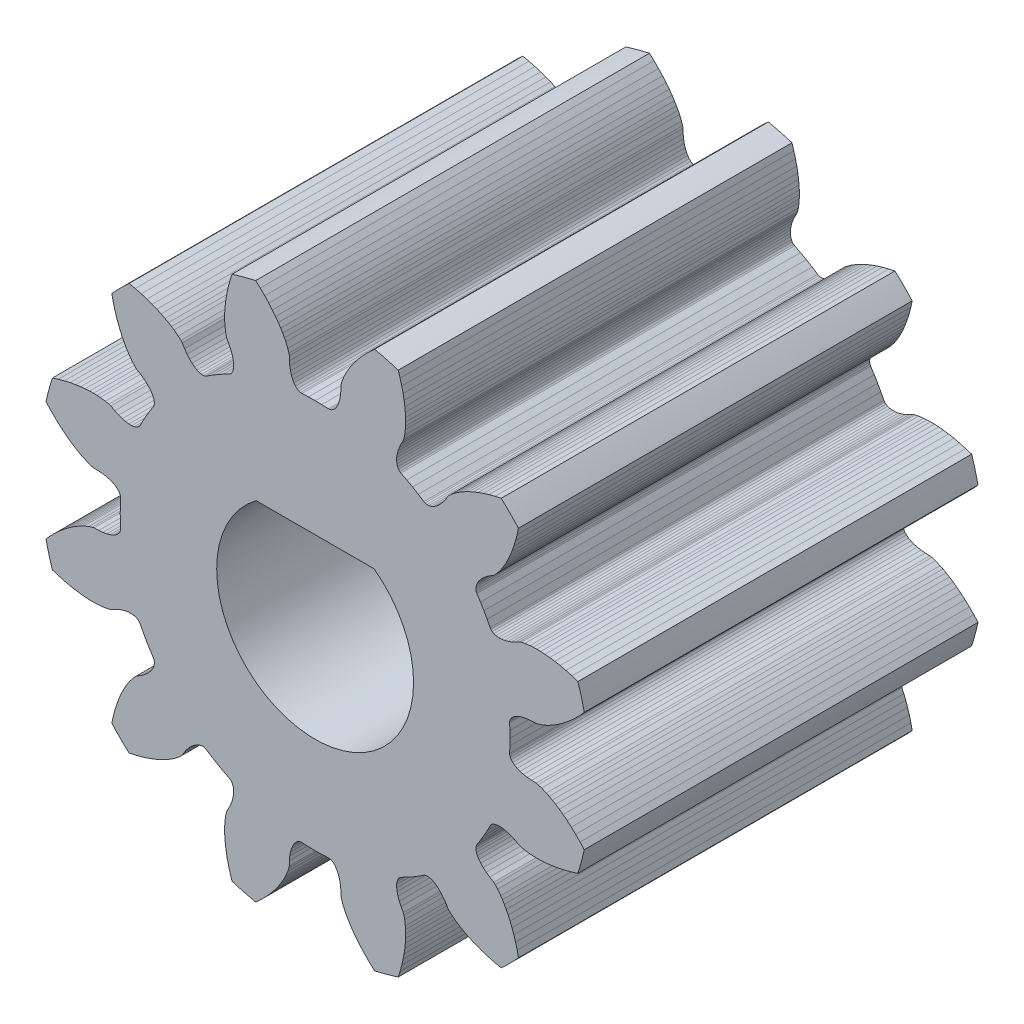
SolidWorks part; units mm, degrees
ref_plane "Front Plane" through (0, 0, 0) normal (0, 0, 1) x (1, 0, 0)
ref_plane "Top Plane" through (0, 0, 0) normal (0, 1, 0) x (1, 0, 0)
ref_plane "Right Plane" through (0, 0, 0) normal (1, 0, 0) x (0, 0, -1)
sketch "Model" plane through (0, 0, 0) normal (0, 0, 1) x (1, 0, 0)
  line L0 (25.8694, -4.5708) -> (25.9098, -4.4161)
  line L1 (25.9098, -4.4161) -> (25.9538, -4.2725)
  line L2 (25.9538, -4.2725) -> (26.0003, -4.1408)
  line L3 (26.0003, -4.1408) -> (26.0488, -4.0198)
  line L4 (26.0488, -4.0198) -> (26.0977, -3.9112)
  line L5 (26.0977, -3.9112) -> (26.1475, -3.8119)
  line L6 (26.1475, -3.8119) -> (26.1956, -3.7252)
  line L7 (26.1956, -3.7252) -> (26.2429, -3.6478)
  line L8 (26.2429, -3.6478) -> (26.2875, -3.5813)
  line L9 (26.2875, -3.5813) -> (26.3671, -3.477)
  line L10 (26.3671, -3.477) -> (26.4285, -3.4089)
  line L11 (26.4285, -3.4089) -> (26.466, -3.3746)
  line L12 (26.466, -3.3746) -> (26.5668, -3.3141)
  line L13 (26.5668, -3.3141) -> (26.6547, -3.2516)
  line L14 (26.6547, -3.2516) -> (26.7296, -3.1879)
  line L15 (26.7296, -3.1879) -> (26.7917, -3.1241)
  line L16 (26.7917, -3.1241) -> (26.841, -3.0611)
  line L17 (26.841, -3.0611) -> (26.8779, -2.9999)
  line L18 (26.8779, -2.9999) -> (26.9025, -2.9414)
  line L19 (26.9025, -2.9414) -> (26.9152, -2.8864)
  line L20 (26.9152, -2.8864) -> (26.9163, -2.836)
  line L21 (26.9163, -2.836) -> (26.9062, -2.7909)
  line L22 (26.9062, -2.7909) -> (26.8916, -2.7611)
  line L23 (26.8916, -2.7611) -> (26.8003, -2.6202)
  line L24 (26.8003, -2.6202) -> (26.7132, -2.475)
  line L25 (26.7132, -2.475) -> (26.631, -2.327)
  line L26 (26.631, -2.327) -> (26.5546, -2.1774)
  line L27 (26.5546, -2.1774) -> (26.5361, -2.1499)
  line L28 (26.5361, -2.1499) -> (26.5021, -2.1186)
  line L29 (26.5021, -2.1186) -> (26.4579, -2.0943)
  line L30 (26.4579, -2.0943) -> (26.404, -2.0778)
  line L31 (26.404, -2.0778) -> (26.341, -2.0699)
  line L32 (26.341, -2.0699) -> (26.2695, -2.0712)
  line L33 (26.2695, -2.0712) -> (26.1903, -2.0825)
  line L34 (26.1903, -2.0825) -> (26.104, -2.1043)
  line L35 (26.104, -2.1043) -> (26.0114, -2.1374)
  line L36 (26.0114, -2.1374) -> (25.9133, -2.1822)
  line L37 (25.9133, -2.1822) -> (25.8106, -2.2393)
  line L38 (25.8106, -2.2393) -> (25.762, -2.2546)
  line L39 (25.762, -2.2546) -> (25.6724, -2.2738)
  line L40 (25.6724, -2.2738) -> (25.5422, -2.2905)
  line L41 (25.5422, -2.2905) -> (25.4624, -2.2959)
  line L42 (25.4624, -2.2959) -> (25.3717, -2.2981)
  line L43 (25.3717, -2.2981) -> (25.2725, -2.2965)
  line L44 (25.2725, -2.2965) -> (25.1616, -2.2899)
  line L45 (25.1616, -2.2899) -> (25.0431, -2.278)
  line L46 (25.0431, -2.278) -> (24.9141, -2.2595)
  line L47 (24.9141, -2.2595) -> (24.7768, -2.2339)
  line L48 (24.7768, -2.2339) -> (24.6305, -2.2002)
  line L49 (24.6305, -2.2002) -> (24.4762, -2.1578)
  line L50 (24.4762, -2.1578) -> (24.3255, -2.1096)
  line L51 (24.1649, -1.5103) -> (24.2713, -1.3932)
  line L52 (24.2713, -1.3932) -> (24.3837, -1.2793)
  line L53 (24.3837, -1.2793) -> (24.4936, -1.177)
  line L54 (24.4936, -1.177) -> (24.5997, -1.0861)
  line L55 (24.5997, -1.0861) -> (24.7022, -1.0056)
  line L56 (24.7022, -1.0056) -> (24.7988, -0.9361)
  line L57 (24.7988, -0.9361) -> (24.8916, -0.875)
  line L58 (24.8916, -0.875) -> (24.9767, -0.8239)
  line L59 (24.9767, -0.8239) -> (25.0563, -0.7805)
  line L60 (25.0563, -0.7805) -> (25.1282, -0.7452)
  line L61 (25.1282, -0.7452) -> (25.2493, -0.6947)
  line L62 (25.2493, -0.6947) -> (25.3365, -0.6665)
  line L63 (25.3365, -0.6665) -> (25.3862, -0.6555)
  line L64 (25.3862, -0.6555) -> (25.5037, -0.6535)
  line L65 (25.5037, -0.6535) -> (25.611, -0.6433)
  line L66 (25.611, -0.6433) -> (25.7078, -0.6256)
  line L67 (25.7078, -0.6256) -> (25.7934, -0.6014)
  line L68 (25.7934, -0.6014) -> (25.8677, -0.5716)
  line L69 (25.8677, -0.5716) -> (25.9302, -0.537)
  line L70 (25.9302, -0.537) -> (25.9808, -0.4986)
  line L71 (25.9808, -0.4986) -> (26.0192, -0.4573)
  line L72 (26.0192, -0.4573) -> (26.0454, -0.4142)
  line L73 (26.0454, -0.4142) -> (26.0592, -0.3701)
  line L74 (26.0592, -0.3701) -> (26.0614, -0.337)
  line L75 (26.0614, -0.337) -> (26.0529, -0.1693)
  line L76 (26.0529, -0.1693) -> (26.05, 0)
  line L77 (26.05, 0) -> (26.0529, 0.1693)
  line L78 (26.0529, 0.1693) -> (26.0614, 0.337)
  line L79 (26.0614, 0.337) -> (26.0592, 0.3701)
  line L80 (26.0592, 0.3701) -> (26.0454, 0.4142)
  line L81 (26.0454, 0.4142) -> (26.0192, 0.4573)
  line L82 (26.0192, 0.4573) -> (25.9808, 0.4986)
  line L83 (25.9808, 0.4986) -> (25.9302, 0.537)
  line L84 (25.9302, 0.537) -> (25.8677, 0.5716)
  line L85 (25.8677, 0.5716) -> (25.7934, 0.6014)
  line L86 (25.7934, 0.6014) -> (25.7078, 0.6256)
  line L87 (25.7078, 0.6256) -> (25.611, 0.6433)
  line L88 (25.611, 0.6433) -> (25.5037, 0.6535)
  line L89 (25.5037, 0.6535) -> (25.3862, 0.6555)
  line L90 (25.3862, 0.6555) -> (25.3365, 0.6665)
  line L91 (25.3365, 0.6665) -> (25.2493, 0.6947)
  line L92 (25.2493, 0.6947) -> (25.1282, 0.7452)
  line L93 (25.1282, 0.7452) -> (25.0563, 0.7805)
  line L94 (25.0563, 0.7805) -> (24.9767, 0.8239)
  line L95 (24.9767, 0.8239) -> (24.8916, 0.875)
  line L96 (24.8916, 0.875) -> (24.7988, 0.9361)
  line L97 (24.7988, 0.9361) -> (24.7022, 1.0056)
  line L98 (24.7022, 1.0056) -> (24.5997, 1.0861)
  line L99 (24.5997, 1.0861) -> (24.4936, 1.177)
  line L100 (24.4936, 1.177) -> (24.3837, 1.2793)
  line L101 (24.3837, 1.2793) -> (24.2713, 1.3932)
  line L102 (24.2713, 1.3932) -> (24.1649, 1.5103)
  line L103 (24.3255, 2.1096) -> (24.4762, 2.1578)
  line L104 (24.4762, 2.1578) -> (24.6305, 2.2002)
  line L105 (24.6305, 2.2002) -> (24.7768, 2.2339)
  line L106 (24.7768, 2.2339) -> (24.9141, 2.2595)
  line L107 (24.9141, 2.2595) -> (25.0431, 2.278)
  line L108 (25.0431, 2.278) -> (25.1616, 2.2899)
  line L109 (25.1616, 2.2899) -> (25.2725, 2.2965)
  line L110 (25.2725, 2.2965) -> (25.3717, 2.2981)
  line L111 (25.3717, 2.2981) -> (25.4624, 2.2959)
  line L112 (25.4624, 2.2959) -> (25.5422, 2.2905)
  line L113 (25.5422, 2.2905) -> (25.6724, 2.2738)
  line L114 (25.6724, 2.2738) -> (25.762, 2.2546)
  line L115 (25.762, 2.2546) -> (25.8106, 2.2393)
  line L116 (25.8106, 2.2393) -> (25.9133, 2.1822)
  line L117 (25.9133, 2.1822) -> (26.0114, 2.1374)
  line L118 (26.0114, 2.1374) -> (26.104, 2.1043)
  line L119 (26.104, 2.1043) -> (26.1903, 2.0825)
  line L120 (26.1903, 2.0825) -> (26.2695, 2.0712)
  line L121 (26.2695, 2.0712) -> (26.341, 2.0699)
  line L122 (26.341, 2.0699) -> (26.404, 2.0778)
  line L123 (26.404, 2.0778) -> (26.4579, 2.0943)
  line L124 (26.4579, 2.0943) -> (26.5021, 2.1186)
  line L125 (26.5021, 2.1186) -> (26.5361, 2.1499)
  line L126 (26.5361, 2.1499) -> (26.5546, 2.1774)
  line L127 (26.5546, 2.1774) -> (26.631, 2.327)
  line L128 (26.631, 2.327) -> (26.7132, 2.475)
  line L129 (26.7132, 2.475) -> (26.8003, 2.6202)
  line L130 (26.8003, 2.6202) -> (26.8916, 2.7611)
  line L131 (26.8916, 2.7611) -> (26.9062, 2.7909)
  line L132 (26.9062, 2.7909) -> (26.9163, 2.836)
  line L133 (26.9163, 2.836) -> (26.9152, 2.8864)
  line L134 (26.9152, 2.8864) -> (26.9025, 2.9414)
  line L135 (26.9025, 2.9414) -> (26.8779, 2.9999)
  line L136 (26.8779, 2.9999) -> (26.841, 3.0611)
  line L137 (26.841, 3.0611) -> (26.7917, 3.1241)
  line L138 (26.7917, 3.1241) -> (26.7296, 3.1879)
  line L139 (26.7296, 3.1879) -> (26.6547, 3.2516)
  line L140 (26.6547, 3.2516) -> (26.5668, 3.3141)
  line L141 (26.5668, 3.3141) -> (26.466, 3.3746)
  line L142 (26.466, 3.3746) -> (26.4285, 3.4089)
  line L143 (26.4285, 3.4089) -> (26.3671, 3.477)
  line L144 (26.3671, 3.477) -> (26.2875, 3.5813)
  line L145 (26.2875, 3.5813) -> (26.2429, 3.6478)
  line L146 (26.2429, 3.6478) -> (26.1956, 3.7252)
  line L147 (26.1956, 3.7252) -> (26.1475, 3.8119)
  line L148 (26.1475, 3.8119) -> (26.0977, 3.9112)
  line L149 (26.0977, 3.9112) -> (26.0488, 4.0198)
  line L150 (26.0488, 4.0198) -> (26.0003, 4.1408)
  line L151 (26.0003, 4.1408) -> (25.9538, 4.2725)
  line L152 (25.9538, 4.2725) -> (25.9098, 4.4161)
  line L153 (25.9098, 4.4161) -> (25.8694, 4.5708)
  line L154 (25.8694, 4.5708) -> (25.8358, 4.7255)
  line L155 (26.2745, 5.1642) -> (26.4292, 5.1306)
  line L156 (26.4292, 5.1306) -> (26.5839, 5.0902)
  line L157 (26.5839, 5.0902) -> (26.7275, 5.0462)
  line L158 (26.7275, 5.0462) -> (26.8592, 4.9997)
  line L159 (26.8592, 4.9997) -> (26.9802, 4.9512)
  line L160 (26.9802, 4.9512) -> (27.0888, 4.9023)
  line L161 (27.0888, 4.9023) -> (27.1881, 4.8525)
  line L162 (27.1881, 4.8525) -> (27.2748, 4.8044)
  line L163 (27.2748, 4.8044) -> (27.3522, 4.7571)
  line L164 (27.3522, 4.7571) -> (27.4187, 4.7125)
  line L165 (27.4187, 4.7125) -> (27.523, 4.6329)
  line L166 (27.523, 4.6329) -> (27.5911, 4.5715)
  line L167 (27.5911, 4.5715) -> (27.6254, 4.534)
  line L168 (27.6254, 4.534) -> (27.6859, 4.4332)
  line L169 (27.6859, 4.4332) -> (27.7484, 4.3453)
  line L170 (27.7484, 4.3453) -> (27.8121, 4.2704)
  line L171 (27.8121, 4.2704) -> (27.8759, 4.2083)
  line L172 (27.8759, 4.2083) -> (27.9389, 4.159)
  line L173 (27.9389, 4.159) -> (28.0001, 4.1221)
  line L174 (28.0001, 4.1221) -> (28.0586, 4.0975)
  line L175 (28.0586, 4.0975) -> (28.1136, 4.0848)
  line L176 (28.1136, 4.0848) -> (28.164, 4.0837)
  line L177 (28.164, 4.0837) -> (28.2091, 4.0938)
  line L178 (28.2091, 4.0938) -> (28.2389, 4.1084)
  line L179 (28.2389, 4.1084) -> (28.3798, 4.1997)
  line L180 (28.3798, 4.1997) -> (28.525, 4.2868)
  line L181 (28.525, 4.2868) -> (28.673, 4.369)
  line L182 (28.673, 4.369) -> (28.8226, 4.4454)
  line L183 (28.8226, 4.4454) -> (28.8501, 4.4639)
  line L184 (28.8501, 4.4639) -> (28.8814, 4.4979)
  line L185 (28.8814, 4.4979) -> (28.9057, 4.5421)
  line L186 (28.9057, 4.5421) -> (28.9222, 4.596)
  line L187 (28.9222, 4.596) -> (28.9301, 4.659)
  line L188 (28.9301, 4.659) -> (28.9288, 4.7305)
  line L189 (28.9288, 4.7305) -> (28.9175, 4.8097)
  line L190 (28.9175, 4.8097) -> (28.8957, 4.896)
  line L191 (28.8957, 4.896) -> (28.8626, 4.9886)
  line L192 (28.8626, 4.9886) -> (28.8178, 5.0867)
  line L193 (28.8178, 5.0867) -> (28.7607, 5.1894)
  line L194 (28.7607, 5.1894) -> (28.7454, 5.238)
  line L195 (28.7454, 5.238) -> (28.7262, 5.3276)
  line L196 (28.7262, 5.3276) -> (28.7095, 5.4578)
  line L197 (28.7095, 5.4578) -> (28.7041, 5.5376)
  line L198 (28.7041, 5.5376) -> (28.7019, 5.6283)
  line L199 (28.7019, 5.6283) -> (28.7035, 5.7275)
  line L200 (28.7035, 5.7275) -> (28.7101, 5.8384)
  line L201 (28.7101, 5.8384) -> (28.722, 5.9569)
  line L202 (28.722, 5.9569) -> (28.7405, 6.0859)
  line L203 (28.7405, 6.0859) -> (28.7661, 6.2232)
  line L204 (28.7661, 6.2232) -> (28.7998, 6.3695)
  line L205 (28.7998, 6.3695) -> (28.8422, 6.5238)
  line L206 (28.8422, 6.5238) -> (28.8904, 6.6745)
  line L207 (29.4897, 6.8351) -> (29.6069, 6.7287)
  line L208 (29.6069, 6.7287) -> (29.7207, 6.6163)
  line L209 (29.7207, 6.6163) -> (29.823, 6.5064)
  line L210 (29.823, 6.5064) -> (29.9139, 6.4003)
  line L211 (29.9139, 6.4003) -> (29.9944, 6.2978)
  line L212 (29.9944, 6.2978) -> (30.0639, 6.2012)
  line L213 (30.0639, 6.2012) -> (30.125, 6.1084)
  line L214 (30.125, 6.1084) -> (30.1761, 6.0233)
  line L215 (30.1761, 6.0233) -> (30.2195, 5.9436)
  line L216 (30.2195, 5.9436) -> (30.2548, 5.8718)
  line L217 (30.2548, 5.8718) -> (30.3053, 5.7507)
  line L218 (30.3053, 5.7507) -> (30.3335, 5.6635)
  line L219 (30.3335, 5.6635) -> (30.3445, 5.6138)
  line L220 (30.3445, 5.6138) -> (30.3465, 5.4963)
  line L221 (30.3465, 5.4963) -> (30.3567, 5.389)
  line L222 (30.3567, 5.389) -> (30.3744, 5.2923)
  line L223 (30.3744, 5.2923) -> (30.3986, 5.2066)
  line L224 (30.3986, 5.2066) -> (30.4285, 5.1323)
  line L225 (30.4285, 5.1323) -> (30.463, 5.0698)
  line L226 (30.463, 5.0698) -> (30.5014, 5.0192)
  line L227 (30.5014, 5.0192) -> (30.5427, 4.9808)
  line L228 (30.5427, 4.9808) -> (30.5858, 4.9546)
  line L229 (30.5858, 4.9546) -> (30.6299, 4.9408)
  line L230 (30.6299, 4.9408) -> (30.663, 4.9386)
  line L231 (30.663, 4.9386) -> (30.8307, 4.9471)
  line L232 (30.8307, 4.9471) -> (31, 4.95)
  line L233 (31, 4.95) -> (31.1693, 4.9471)
  line L234 (31.1693, 4.9471) -> (31.337, 4.9386)
  line L235 (31.337, 4.9386) -> (31.3701, 4.9408)
  line L236 (31.3701, 4.9408) -> (31.4142, 4.9546)
  line L237 (31.4142, 4.9546) -> (31.4573, 4.9808)
  line L238 (31.4573, 4.9808) -> (31.4986, 5.0192)
  line L239 (31.4986, 5.0192) -> (31.537, 5.0698)
  line L240 (31.537, 5.0698) -> (31.5715, 5.1323)
  line L241 (31.5715, 5.1323) -> (31.6014, 5.2066)
  line L242 (31.6014, 5.2066) -> (31.6256, 5.2923)
  line L243 (31.6256, 5.2923) -> (31.6433, 5.389)
  line L244 (31.6433, 5.389) -> (31.6535, 5.4963)
  line L245 (31.6535, 5.4963) -> (31.6555, 5.6138)
  line L246 (31.6555, 5.6138) -> (31.6665, 5.6635)
  line L247 (31.6665, 5.6635) -> (31.6947, 5.7507)
  line L248 (31.6947, 5.7507) -> (31.7452, 5.8718)
  line L249 (31.7452, 5.8718) -> (31.7805, 5.9436)
  line L250 (31.7805, 5.9436) -> (31.8239, 6.0233)
  line L251 (31.8239, 6.0233) -> (31.875, 6.1084)
  line L252 (31.875, 6.1084) -> (31.9361, 6.2012)
  line L253 (31.9361, 6.2012) -> (32.0056, 6.2978)
  line L254 (32.0056, 6.2978) -> (32.0862, 6.4003)
  line L255 (32.0862, 6.4003) -> (32.177, 6.5064)
  line L256 (32.177, 6.5064) -> (32.2793, 6.6163)
  line L257 (32.2793, 6.6163) -> (32.3932, 6.7287)
  line L258 (32.3932, 6.7287) -> (32.5103, 6.8351)
  line L259 (33.1096, 6.6745) -> (33.1578, 6.5238)
  line L260 (33.1578, 6.5238) -> (33.2002, 6.3695)
  line L261 (33.2002, 6.3695) -> (33.2339, 6.2232)
  line L262 (33.2339, 6.2232) -> (33.2595, 6.0859)
  line L263 (33.2595, 6.0859) -> (33.278, 5.9569)
  line L264 (33.278, 5.9569) -> (33.2899, 5.8384)
  line L265 (33.2899, 5.8384) -> (33.2965, 5.7275)
  line L266 (33.2965, 5.7275) -> (33.2981, 5.6283)
  line L267 (33.2981, 5.6283) -> (33.2959, 5.5376)
  line L268 (33.2959, 5.5376) -> (33.2905, 5.4578)
  line L269 (33.2905, 5.4578) -> (33.2738, 5.3276)
  line L270 (33.2738, 5.3276) -> (33.2546, 5.238)
  line L271 (33.2546, 5.238) -> (33.2393, 5.1894)
  line L272 (33.2393, 5.1894) -> (33.1822, 5.0867)
  line L273 (33.1822, 5.0867) -> (33.1374, 4.9886)
  line L274 (33.1374, 4.9886) -> (33.1043, 4.896)
  line L275 (33.1043, 4.896) -> (33.0825, 4.8097)
  line L276 (33.0825, 4.8097) -> (33.0712, 4.7305)
  line L277 (33.0712, 4.7305) -> (33.0699, 4.659)
  line L278 (33.0699, 4.659) -> (33.0778, 4.596)
  line L279 (33.0778, 4.596) -> (33.0943, 4.5421)
  line L280 (33.0943, 4.5421) -> (33.1186, 4.4979)
  line L281 (33.1186, 4.4979) -> (33.1499, 4.4639)
  line L282 (33.1499, 4.4639) -> (33.1774, 4.4454)
  line L283 (33.1774, 4.4454) -> (33.327, 4.369)
  line L284 (33.327, 4.369) -> (33.475, 4.2868)
  line L285 (33.475, 4.2868) -> (33.6202, 4.1997)
  line L286 (33.6202, 4.1997) -> (33.7611, 4.1084)
  line L287 (33.7611, 4.1084) -> (33.7909, 4.0938)
  line L288 (33.7909, 4.0938) -> (33.836, 4.0837)
  line L289 (33.836, 4.0837) -> (33.8864, 4.0848)
  line L290 (33.8864, 4.0848) -> (33.9414, 4.0975)
  line L291 (33.9414, 4.0975) -> (33.9999, 4.1221)
  line L292 (33.9999, 4.1221) -> (34.0611, 4.159)
  line L293 (34.0611, 4.159) -> (34.1241, 4.2083)
  line L294 (34.1241, 4.2083) -> (34.1879, 4.2704)
  line L295 (34.1879, 4.2704) -> (34.2516, 4.3453)
  line L296 (34.2516, 4.3453) -> (34.3141, 4.4332)
  line L297 (34.3141, 4.4332) -> (34.3746, 4.534)
  line L298 (34.3746, 4.534) -> (34.4089, 4.5715)
  line L299 (34.4089, 4.5715) -> (34.477, 4.6329)
  line L300 (34.477, 4.6329) -> (34.5813, 4.7125)
  line L301 (34.5813, 4.7125) -> (34.6478, 4.7571)
  line L302 (34.6478, 4.7571) -> (34.7252, 4.8044)
  line L303 (34.7252, 4.8044) -> (34.8119, 4.8525)
  line L304 (34.8119, 4.8525) -> (34.9112, 4.9023)
  line L305 (34.9112, 4.9023) -> (35.0198, 4.9512)
  line L306 (35.0198, 4.9512) -> (35.1408, 4.9997)
  line L307 (35.1408, 4.9997) -> (35.2725, 5.0462)
  line L308 (35.2725, 5.0462) -> (35.4161, 5.0902)
  line L309 (35.4161, 5.0902) -> (35.5708, 5.1306)
  line L310 (35.5708, 5.1306) -> (35.7255, 5.1642)
  line L311 (36.1642, 4.7255) -> (36.1306, 4.5708)
  line L312 (36.1306, 4.5708) -> (36.0902, 4.4161)
  line L313 (36.0902, 4.4161) -> (36.0462, 4.2725)
  line L314 (36.0462, 4.2725) -> (35.9997, 4.1408)
  line L315 (35.9997, 4.1408) -> (35.9512, 4.0198)
  line L316 (35.9512, 4.0198) -> (35.9023, 3.9112)
  line L317 (35.9023, 3.9112) -> (35.8525, 3.8119)
  line L318 (35.8525, 3.8119) -> (35.8044, 3.7252)
  line L319 (35.8044, 3.7252) -> (35.7571, 3.6478)
  line L320 (35.7571, 3.6478) -> (35.7125, 3.5813)
  line L321 (35.7125, 3.5813) -> (35.6329, 3.477)
  line L322 (35.6329, 3.477) -> (35.5715, 3.4089)
  line L323 (35.5715, 3.4089) -> (35.534, 3.3746)
  line L324 (35.534, 3.3746) -> (35.4332, 3.3141)
  line L325 (35.4332, 3.3141) -> (35.3453, 3.2516)
  line L326 (35.3453, 3.2516) -> (35.2704, 3.1879)
  line L327 (35.2704, 3.1879) -> (35.2083, 3.1241)
  line L328 (35.2083, 3.1241) -> (35.159, 3.0611)
  line L329 (35.159, 3.0611) -> (35.1221, 2.9999)
  line L330 (35.1221, 2.9999) -> (35.0975, 2.9414)
  line L331 (35.0975, 2.9414) -> (35.0848, 2.8864)
  line L332 (35.0848, 2.8864) -> (35.0837, 2.836)
  line L333 (35.0837, 2.836) -> (35.0938, 2.7909)
  line L334 (35.0938, 2.7909) -> (35.1084, 2.7611)
  line L335 (35.1084, 2.7611) -> (35.1997, 2.6202)
  line L336 (35.1997, 2.6202) -> (35.2868, 2.475)
  line L337 (35.2868, 2.475) -> (35.369, 2.327)
  line L338 (35.369, 2.327) -> (35.4454, 2.1774)
  line L339 (35.4454, 2.1774) -> (35.4639, 2.1499)
  line L340 (35.4639, 2.1499) -> (35.4979, 2.1186)
  line L341 (35.4979, 2.1186) -> (35.5421, 2.0943)
  line L342 (35.5421, 2.0943) -> (35.596, 2.0778)
  line L343 (35.596, 2.0778) -> (35.659, 2.0699)
  line L344 (35.659, 2.0699) -> (35.7305, 2.0712)
  line L345 (35.7305, 2.0712) -> (35.8097, 2.0825)
  line L346 (35.8097, 2.0825) -> (35.896, 2.1043)
  line L347 (35.896, 2.1043) -> (35.9886, 2.1374)
  line L348 (35.9886, 2.1374) -> (36.0867, 2.1822)
  line L349 (36.0867, 2.1822) -> (36.1894, 2.2393)
  line L350 (36.1894, 2.2393) -> (36.238, 2.2546)
  line L351 (36.238, 2.2546) -> (36.3276, 2.2738)
  line L352 (36.3276, 2.2738) -> (36.4578, 2.2905)
  line L353 (36.4578, 2.2905) -> (36.5376, 2.2959)
  line L354 (36.5376, 2.2959) -> (36.6283, 2.2981)
  line L355 (36.6283, 2.2981) -> (36.7275, 2.2965)
  line L356 (36.7275, 2.2965) -> (36.8384, 2.2899)
  line L357 (36.8384, 2.2899) -> (36.9569, 2.278)
  line L358 (36.9569, 2.278) -> (37.0859, 2.2595)
  line L359 (37.0859, 2.2595) -> (37.2232, 2.2339)
  line L360 (37.2232, 2.2339) -> (37.3695, 2.2002)
  line L361 (37.3695, 2.2002) -> (37.5238, 2.1578)
  line L362 (37.5238, 2.1578) -> (37.6745, 2.1096)
  line L363 (37.8351, 1.5103) -> (37.7287, 1.3932)
  line L364 (37.7287, 1.3932) -> (37.6163, 1.2793)
  line L365 (37.6163, 1.2793) -> (37.5064, 1.177)
  line L366 (37.5064, 1.177) -> (37.4003, 1.0861)
  line L367 (37.4003, 1.0861) -> (37.2978, 1.0056)
  line L368 (37.2978, 1.0056) -> (37.2012, 0.9361)
  line L369 (37.2012, 0.9361) -> (37.1084, 0.875)
  line L370 (37.1084, 0.875) -> (37.0233, 0.8239)
  line L371 (37.0233, 0.8239) -> (36.9436, 0.7805)
  line L372 (36.9436, 0.7805) -> (36.8718, 0.7452)
  line L373 (36.8718, 0.7452) -> (36.7507, 0.6947)
  line L374 (36.7507, 0.6947) -> (36.6635, 0.6665)
  line L375 (36.6635, 0.6665) -> (36.6138, 0.6555)
  line L376 (36.6138, 0.6555) -> (36.4963, 0.6535)
  line L377 (36.4963, 0.6535) -> (36.389, 0.6433)
  line L378 (36.389, 0.6433) -> (36.2923, 0.6256)
  line L379 (36.2923, 0.6256) -> (36.2066, 0.6014)
  line L380 (36.2066, 0.6014) -> (36.1323, 0.5716)
  line L381 (36.1323, 0.5716) -> (36.0698, 0.537)
  line L382 (36.0698, 0.537) -> (36.0192, 0.4986)
  line L383 (36.0192, 0.4986) -> (35.9808, 0.4573)
  line L384 (35.9808, 0.4573) -> (35.9546, 0.4142)
  line L385 (35.9546, 0.4142) -> (35.9408, 0.3701)
  line L386 (35.9408, 0.3701) -> (35.9386, 0.337)
  line L387 (35.9386, 0.337) -> (35.9471, 0.1693)
  line L388 (35.9471, 0.1693) -> (35.95, 0)
  line L389 (35.95, 0) -> (35.9471, -0.1693)
  line L390 (35.9471, -0.1693) -> (35.9386, -0.337)
  line L391 (35.9386, -0.337) -> (35.9408, -0.3701)
  line L392 (35.9408, -0.3701) -> (35.9546, -0.4142)
  line L393 (35.9546, -0.4142) -> (35.9808, -0.4573)
  line L394 (35.9808, -0.4573) -> (36.0192, -0.4986)
  line L395 (36.0192, -0.4986) -> (36.0698, -0.537)
  line L396 (36.0698, -0.537) -> (36.1323, -0.5716)
  line L397 (36.1323, -0.5716) -> (36.2066, -0.6014)
  line L398 (36.2066, -0.6014) -> (36.2923, -0.6256)
  line L399 (36.2923, -0.6256) -> (36.389, -0.6433)
  line L400 (36.389, -0.6433) -> (36.4963, -0.6535)
  line L401 (36.4963, -0.6535) -> (36.6138, -0.6555)
  line L402 (36.6138, -0.6555) -> (36.6635, -0.6665)
  line L403 (36.6635, -0.6665) -> (36.7507, -0.6947)
  line L404 (36.7507, -0.6947) -> (36.8718, -0.7452)
  line L405 (36.8718, -0.7452) -> (36.9436, -0.7805)
  line L406 (36.9436, -0.7805) -> (37.0233, -0.8239)
  line L407 (37.0233, -0.8239) -> (37.1084, -0.875)
  line L408 (37.1084, -0.875) -> (37.2012, -0.9361)
  line L409 (37.2012, -0.9361) -> (37.2978, -1.0056)
  line L410 (37.2978, -1.0056) -> (37.4003, -1.0861)
  line L411 (37.4003, -1.0861) -> (37.5064, -1.177)
  line L412 (37.5064, -1.177) -> (37.6163, -1.2793)
  line L413 (37.6163, -1.2793) -> (37.7287, -1.3932)
  line L414 (37.7287, -1.3932) -> (37.8351, -1.5103)
  line L415 (37.6745, -2.1096) -> (37.5238, -2.1578)
  line L416 (37.5238, -2.1578) -> (37.3695, -2.2002)
  line L417 (37.3695, -2.2002) -> (37.2232, -2.2339)
  line L418 (37.2232, -2.2339) -> (37.0859, -2.2595)
  line L419 (37.0859, -2.2595) -> (36.9569, -2.278)
  line L420 (36.9569, -2.278) -> (36.8384, -2.2899)
  line L421 (36.8384, -2.2899) -> (36.7275, -2.2965)
  line L422 (36.7275, -2.2965) -> (36.6283, -2.2981)
  line L423 (36.6283, -2.2981) -> (36.5376, -2.2959)
  line L424 (36.5376, -2.2959) -> (36.4578, -2.2905)
  line L425 (36.4578, -2.2905) -> (36.3276, -2.2738)
  line L426 (36.3276, -2.2738) -> (36.238, -2.2546)
  line L427 (36.238, -2.2546) -> (36.1894, -2.2393)
  line L428 (36.1894, -2.2393) -> (36.0867, -2.1822)
  line L429 (36.0867, -2.1822) -> (35.9886, -2.1374)
  line L430 (35.9886, -2.1374) -> (35.896, -2.1043)
  line L431 (35.896, -2.1043) -> (35.8097, -2.0825)
  line L432 (35.8097, -2.0825) -> (35.7305, -2.0712)
  line L433 (35.7305, -2.0712) -> (35.659, -2.0699)
  line L434 (35.659, -2.0699) -> (35.596, -2.0778)
  line L435 (35.596, -2.0778) -> (35.5421, -2.0943)
  line L436 (35.5421, -2.0943) -> (35.4979, -2.1186)
  line L437 (35.4979, -2.1186) -> (35.4639, -2.1499)
  line L438 (35.4639, -2.1499) -> (35.4454, -2.1774)
  line L439 (35.4454, -2.1774) -> (35.369, -2.327)
  line L440 (35.369, -2.327) -> (35.2868, -2.475)
  line L441 (35.2868, -2.475) -> (35.1997, -2.6202)
  line L442 (35.1997, -2.6202) -> (35.1084, -2.7611)
  line L443 (35.1084, -2.7611) -> (35.0938, -2.7909)
  line L444 (35.0938, -2.7909) -> (35.0837, -2.836)
  line L445 (35.0837, -2.836) -> (35.0848, -2.8864)
  line L446 (35.0848, -2.8864) -> (35.0975, -2.9414)
  line L447 (35.0975, -2.9414) -> (35.1221, -2.9999)
  line L448 (35.1221, -2.9999) -> (35.159, -3.0611)
  line L449 (35.159, -3.0611) -> (35.2083, -3.1241)
  line L450 (35.2083, -3.1241) -> (35.2704, -3.1879)
  line L451 (35.2704, -3.1879) -> (35.3453, -3.2516)
  line L452 (35.3453, -3.2516) -> (35.4332, -3.3141)
  line L453 (35.4332, -3.3141) -> (35.534, -3.3746)
  line L454 (35.534, -3.3746) -> (35.5715, -3.4089)
  line L455 (35.5715, -3.4089) -> (35.6329, -3.477)
  line L456 (35.6329, -3.477) -> (35.7125, -3.5813)
  line L457 (35.7125, -3.5813) -> (35.7571, -3.6478)
  line L458 (35.7571, -3.6478) -> (35.8044, -3.7252)
  line L459 (35.8044, -3.7252) -> (35.8525, -3.8119)
  line L460 (35.8525, -3.8119) -> (35.9023, -3.9112)
  line L461 (35.9023, -3.9112) -> (35.9512, -4.0198)
  line L462 (35.9512, -4.0198) -> (35.9997, -4.1408)
  line L463 (35.9997, -4.1408) -> (36.0462, -4.2725)
  line L464 (36.0462, -4.2725) -> (36.0902, -4.4161)
  line L465 (36.0902, -4.4161) -> (36.1306, -4.5708)
  line L466 (36.1306, -4.5708) -> (36.1642, -4.7255)
  line L467 (35.7255, -5.1642) -> (35.5708, -5.1306)
  line L468 (35.5708, -5.1306) -> (35.4161, -5.0902)
  line L469 (35.4161, -5.0902) -> (35.2725, -5.0462)
  line L470 (35.2725, -5.0462) -> (35.1408, -4.9997)
  line L471 (35.1408, -4.9997) -> (35.0198, -4.9512)
  line L472 (35.0198, -4.9512) -> (34.9112, -4.9023)
  line L473 (34.9112, -4.9023) -> (34.8119, -4.8525)
  line L474 (34.8119, -4.8525) -> (34.7252, -4.8044)
  line L475 (34.7252, -4.8044) -> (34.6478, -4.7571)
  line L476 (34.6478, -4.7571) -> (34.5813, -4.7125)
  line L477 (34.5813, -4.7125) -> (34.477, -4.6329)
  line L478 (34.477, -4.6329) -> (34.4089, -4.5715)
  line L479 (34.4089, -4.5715) -> (34.3746, -4.534)
  line L480 (34.3746, -4.534) -> (34.3141, -4.4332)
  line L481 (34.3141, -4.4332) -> (34.2516, -4.3453)
  line L482 (34.2516, -4.3453) -> (34.1879, -4.2704)
  line L483 (34.1879, -4.2704) -> (34.1241, -4.2083)
  line L484 (34.1241, -4.2083) -> (34.0611, -4.159)
  line L485 (34.0611, -4.159) -> (33.9999, -4.1221)
  line L486 (33.9999, -4.1221) -> (33.9414, -4.0975)
  line L487 (33.9414, -4.0975) -> (33.8864, -4.0848)
  line L488 (33.8864, -4.0848) -> (33.836, -4.0837)
  line L489 (33.836, -4.0837) -> (33.7909, -4.0938)
  line L490 (33.7909, -4.0938) -> (33.7611, -4.1084)
  line L491 (33.7611, -4.1084) -> (33.6202, -4.1997)
  line L492 (33.6202, -4.1997) -> (33.475, -4.2868)
  line L493 (33.475, -4.2868) -> (33.327, -4.369)
  line L494 (33.327, -4.369) -> (33.1774, -4.4454)
  line L495 (33.1774, -4.4454) -> (33.1499, -4.4639)
  line L496 (33.1499, -4.4639) -> (33.1186, -4.4979)
  line L497 (33.1186, -4.4979) -> (33.0943, -4.5421)
  line L498 (33.0943, -4.5421) -> (33.0778, -4.596)
  line L499 (33.0778, -4.596) -> (33.0699, -4.659)
  line L500 (33.0699, -4.659) -> (33.0712, -4.7305)
  line L501 (33.0712, -4.7305) -> (33.0825, -4.8097)
  line L502 (33.0825, -4.8097) -> (33.1043, -4.896)
  line L503 (33.1043, -4.896) -> (33.1374, -4.9886)
  line L504 (33.1374, -4.9886) -> (33.1822, -5.0867)
  line L505 (33.1822, -5.0867) -> (33.2393, -5.1894)
  line L506 (33.2393, -5.1894) -> (33.2546, -5.238)
  line L507 (33.2546, -5.238) -> (33.2738, -5.3276)
  line L508 (33.2738, -5.3276) -> (33.2905, -5.4578)
  line L509 (33.2905, -5.4578) -> (33.2959, -5.5376)
  line L510 (33.2959, -5.5376) -> (33.2981, -5.6283)
  line L511 (33.2981, -5.6283) -> (33.2965, -5.7275)
  line L512 (33.2965, -5.7275) -> (33.2899, -5.8384)
  line L513 (33.2899, -5.8384) -> (33.278, -5.9569)
  line L514 (33.278, -5.9569) -> (33.2595, -6.0859)
  line L515 (33.2595, -6.0859) -> (33.2339, -6.2232)
  line L516 (33.2339, -6.2232) -> (33.2002, -6.3695)
  line L517 (33.2002, -6.3695) -> (33.1578, -6.5238)
  line L518 (33.1578, -6.5238) -> (33.1096, -6.6745)
  line L519 (32.5103, -6.8351) -> (32.3932, -6.7287)
  line L520 (32.3932, -6.7287) -> (32.2793, -6.6163)
  line L521 (32.2793, -6.6163) -> (32.177, -6.5064)
  line L522 (32.177, -6.5064) -> (32.0862, -6.4003)
  line L523 (32.0862, -6.4003) -> (32.0056, -6.2978)
  line L524 (32.0056, -6.2978) -> (31.9361, -6.2012)
  line L525 (31.9361, -6.2012) -> (31.875, -6.1084)
  line L526 (31.875, -6.1084) -> (31.8239, -6.0233)
  line L527 (31.8239, -6.0233) -> (31.7805, -5.9436)
  line L528 (31.7805, -5.9436) -> (31.7452, -5.8718)
  line L529 (31.7452, -5.8718) -> (31.6947, -5.7507)
  line L530 (31.6947, -5.7507) -> (31.6665, -5.6635)
  line L531 (31.6665, -5.6635) -> (31.6555, -5.6138)
  line L532 (31.6555, -5.6138) -> (31.6535, -5.4963)
  line L533 (31.6535, -5.4963) -> (31.6433, -5.389)
  line L534 (31.6433, -5.389) -> (31.6256, -5.2923)
  line L535 (31.6256, -5.2923) -> (31.6014, -5.2066)
  line L536 (31.6014, -5.2066) -> (31.5715, -5.1323)
  line L537 (31.5715, -5.1323) -> (31.537, -5.0698)
  line L538 (31.537, -5.0698) -> (31.4986, -5.0192)
  line L539 (31.4986, -5.0192) -> (31.4573, -4.9808)
  line L540 (31.4573, -4.9808) -> (31.4142, -4.9546)
  line L541 (31.4142, -4.9546) -> (31.3701, -4.9408)
  line L542 (31.3701, -4.9408) -> (31.337, -4.9386)
  line L543 (31.337, -4.9386) -> (31.1693, -4.9471)
  line L544 (31.1693, -4.9471) -> (31, -4.95)
  line L545 (31, -4.95) -> (30.8307, -4.9471)
  line L546 (30.8307, -4.9471) -> (30.663, -4.9386)
  line L547 (30.663, -4.9386) -> (30.6299, -4.9408)
  line L548 (30.6299, -4.9408) -> (30.5858, -4.9546)
  line L549 (30.5858, -4.9546) -> (30.5427, -4.9808)
  line L550 (30.5427, -4.9808) -> (30.5014, -5.0192)
  line L551 (30.5014, -5.0192) -> (30.463, -5.0698)
  line L552 (30.463, -5.0698) -> (30.4285, -5.1323)
  line L553 (30.4285, -5.1323) -> (30.3986, -5.2066)
  line L554 (30.3986, -5.2066) -> (30.3744, -5.2923)
  line L555 (30.3744, -5.2923) -> (30.3567, -5.389)
  line L556 (30.3567, -5.389) -> (30.3465, -5.4963)
  line L557 (30.3465, -5.4963) -> (30.3445, -5.6138)
  line L558 (30.3445, -5.6138) -> (30.3335, -5.6635)
  line L559 (30.3335, -5.6635) -> (30.3053, -5.7507)
  line L560 (30.3053, -5.7507) -> (30.2548, -5.8718)
  line L561 (30.2548, -5.8718) -> (30.2195, -5.9436)
  line L562 (30.2195, -5.9436) -> (30.1761, -6.0233)
  line L563 (30.1761, -6.0233) -> (30.125, -6.1084)
  line L564 (30.125, -6.1084) -> (30.0639, -6.2012)
  line L565 (30.0639, -6.2012) -> (29.9944, -6.2978)
  line L566 (29.9944, -6.2978) -> (29.9139, -6.4003)
  line L567 (29.9139, -6.4003) -> (29.823, -6.5064)
  line L568 (29.823, -6.5064) -> (29.7207, -6.6163)
  line L569 (29.7207, -6.6163) -> (29.6069, -6.7287)
  line L570 (29.6069, -6.7287) -> (29.4897, -6.8351)
  line L571 (28.8904, -6.6745) -> (28.8422, -6.5238)
  line L572 (28.8422, -6.5238) -> (28.7998, -6.3695)
  line L573 (28.7998, -6.3695) -> (28.7661, -6.2232)
  line L574 (28.7661, -6.2232) -> (28.7405, -6.0859)
  line L575 (28.7405, -6.0859) -> (28.722, -5.9569)
  line L576 (28.722, -5.9569) -> (28.7101, -5.8384)
  line L577 (28.7101, -5.8384) -> (28.7035, -5.7275)
  line L578 (28.7035, -5.7275) -> (28.7019, -5.6283)
  line L579 (28.7019, -5.6283) -> (28.7041, -5.5376)
  line L580 (28.7041, -5.5376) -> (28.7095, -5.4578)
  line L581 (28.7095, -5.4578) -> (28.7262, -5.3276)
  line L582 (28.7262, -5.3276) -> (28.7454, -5.238)
  line L583 (28.7454, -5.238) -> (28.7607, -5.1894)
  line L584 (28.7607, -5.1894) -> (28.8178, -5.0867)
  line L585 (28.8178, -5.0867) -> (28.8626, -4.9886)
  line L586 (28.8626, -4.9886) -> (28.8957, -4.896)
  line L587 (28.8957, -4.896) -> (28.9175, -4.8097)
  line L588 (28.9175, -4.8097) -> (28.9288, -4.7305)
  line L589 (28.9288, -4.7305) -> (28.9301, -4.659)
  line L590 (28.9301, -4.659) -> (28.9222, -4.596)
  line L591 (28.9222, -4.596) -> (28.9057, -4.5421)
  line L592 (28.9057, -4.5421) -> (28.8814, -4.4979)
  line L593 (28.8814, -4.4979) -> (28.8501, -4.4639)
  line L594 (28.8501, -4.4639) -> (28.8226, -4.4454)
  line L595 (28.8226, -4.4454) -> (28.673, -4.369)
  line L596 (28.673, -4.369) -> (28.525, -4.2868)
  line L597 (28.525, -4.2868) -> (28.3798, -4.1997)
  line L598 (28.3798, -4.1997) -> (28.2389, -4.1084)
  line L599 (28.2389, -4.1084) -> (28.2091, -4.0938)
  line L600 (28.2091, -4.0938) -> (28.164, -4.0837)
  line L601 (28.164, -4.0837) -> (28.1136, -4.0848)
  line L602 (28.1136, -4.0848) -> (28.0586, -4.0975)
  line L603 (28.0586, -4.0975) -> (28.0001, -4.1221)
  line L604 (28.0001, -4.1221) -> (27.9389, -4.159)
  line L605 (27.9389, -4.159) -> (27.8759, -4.2083)
  line L606 (27.8759, -4.2083) -> (27.8121, -4.2704)
  line L607 (27.8121, -4.2704) -> (27.7484, -4.3453)
  line L608 (27.7484, -4.3453) -> (27.6859, -4.4332)
  line L609 (27.6859, -4.4332) -> (27.6254, -4.534)
  line L610 (27.6254, -4.534) -> (27.5911, -4.5715)
  line L611 (27.5911, -4.5715) -> (27.523, -4.6329)
  line L612 (27.523, -4.6329) -> (27.4187, -4.7125)
  line L613 (27.4187, -4.7125) -> (27.3522, -4.7571)
  line L614 (27.3522, -4.7571) -> (27.2748, -4.8044)
  line L615 (27.2748, -4.8044) -> (27.1881, -4.8525)
  line L616 (27.1881, -4.8525) -> (27.0888, -4.9023)
  line L617 (27.0888, -4.9023) -> (26.9802, -4.9512)
  line L618 (26.9802, -4.9512) -> (26.8592, -4.9997)
  line L619 (26.8592, -4.9997) -> (26.7275, -5.0462)
  line L620 (26.7275, -5.0462) -> (26.5839, -5.0902)
  line L621 (26.5839, -5.0902) -> (26.4292, -5.1306)
  line L622 (26.4292, -5.1306) -> (26.2745, -5.1642)
  line L623 (25.8358, -4.7255) -> (25.8694, -4.5708)
  arc A0 (24.1649, -1.5103) -> (24.3255, -2.1096) centre (31, 0) ccw
  arc A1 (24.3255, 2.1096) -> (24.1649, 1.5103) centre (31, 0) ccw
  arc A2 (26.2745, 5.1642) -> (25.8358, 4.7255) centre (31, 0) ccw
  arc A3 (29.4897, 6.8351) -> (28.8904, 6.6745) centre (31, 0) ccw
  arc A4 (33.1096, 6.6745) -> (32.5103, 6.8351) centre (31, 0) ccw
  arc A5 (36.1642, 4.7255) -> (35.7255, 5.1642) centre (31, 0) ccw
  arc A6 (37.8351, 1.5103) -> (37.6745, 2.1096) centre (31, 0) ccw
  arc A7 (37.6745, -2.1096) -> (37.8351, -1.5103) centre (31, 0) ccw
  arc A8 (35.7255, -5.1642) -> (36.1642, -4.7255) centre (31, 0) ccw
  arc A9 (32.5103, -6.8351) -> (33.1096, -6.6745) centre (31, 0) ccw
  arc A10 (28.8904, -6.6745) -> (29.4897, -6.8351) centre (31, 0) ccw
  arc A11 (25.8358, -4.7255) -> (26.2745, -5.1642) centre (31, 0) ccw
extrude "Boss-Extrude1" add sketch "Model" along normal blind 10
ref_point "Point2"
ref_axis "Axis1" through (31, 0, 10) along (0, 0, 1)
sketch "Sketch3" plane through (0, 0, 10) normal (0, 0, 1) x (1, 0, 0)
  circle A0 centre (31, 0) radius 2.5
  dimension "D1" = 5
extrude "Cut-Extrude1" cut sketch "Sketch3" against normal through all
sketch "Sketch4" plane through (0, 0, 10) normal (0, 0, 1) x (1, 0, 0)
  line L1 (28.0478, 3.6919) -> (33.9636, 3.6919)
  line L2 (28.0478, 3.6919) -> (28.0478, 2)
  line L3 (28.0478, 2) -> (33.9636, 2)
  line L4 (33.9636, 3.6919) -> (33.9636, 2)
  circle A0 centre (31, 0) radius 2.5 construction
  dimension "D1" = 2
  dimension "D4" = 2.9522
  dimension "D2" = 5.9158
  dimension "D3" = 1.6919
extrude "Boss-Extrude2" add sketch "Sketch4" against normal blind 10
